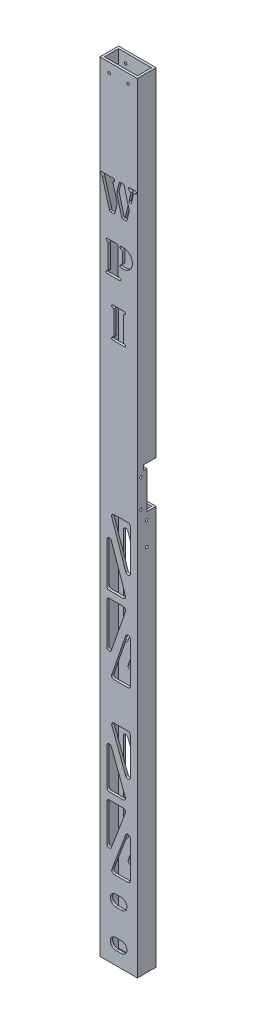
SolidWorks part; units mm, degrees
material "6061-T6 (SS)"
ref_plane "Front Plane" through (0, 0, 0) normal (0, 0, 1) x (1, 0, 0)
ref_plane "Top Plane" through (0, 0, 0) normal (0, 1, 0) x (1, 0, 0)
ref_plane "Right Plane" through (0, 0, 0) normal (1, 0, 0) x (0, 0, -1)
sketch "Sketch1" plane through (0, 0, 0) normal (0, 1, 0) x (1, 0, 0)
  line L0 (-22.225, 9.525) -> (-22.225, 12.7) construction
  line L1 (-25.4, -12.7) -> (25.4, -12.7)
  line L2 (-25.4, -12.7) -> (-25.4, 12.7)
  line L3 (-25.4, 12.7) -> (25.4, 12.7)
  line L4 (25.4, -12.7) -> (25.4, 12.7)
  line L5 (-25.4, -12.7) -> (25.4, 12.7) construction
  line L6 (-25.4, 12.7) -> (25.4, -12.7) construction
  line L7 (-22.225, -9.525) -> (22.225, -9.525)
  line L8 (-22.225, -9.525) -> (-22.225, 9.525)
  line L9 (-22.225, 9.525) -> (22.225, 9.525)
  line L10 (22.225, -9.525) -> (22.225, 9.525)
  line L11 (-22.225, -9.525) -> (22.225, 9.525) construction
  line L12 (-22.225, 9.525) -> (22.225, -9.525) construction
  line L13 (-22.225, 9.525) -> (-25.4, 9.525) construction
  point P0 (0, 0)
  point P6 (0, 0)
  dimension "D1" = 50.8
  dimension "D2" = 25.4
  dimension "D3" = 3.175
extrude "Boss-Extrude1" add sketch "Sketch1" along normal mid plane 591.185
hole_wizard "M8 Clearance Hole1" positions "Sketch3" profile "Sketch4" hole size "M8" standard "ANSI Metric" end condition through all
sketch "Sketch3" plane through (0, 0, 12.7) normal (0, 0, 1) x (1, 0, 0)
  line L1 (-25.4, -295.5925) -> (25.4, -295.5925) construction
  line L2 (0, -193.9925) -> (-50000, -193.9925) construction
  line L3 (-3.8049, -270.1925) -> (-3.8049, -295.5925) construction
  line L6 (-3.8049, -219.3925) -> (-3.8049, -193.9925) construction
  line L7 (0, 0) -> (0, 50000) construction
  point P0 (-3.8049, -270.1925)
  point P2 (-3.8049, -219.3925)
  point P29 (3.8049, -219.3925)
  point P31 (3.8049, -270.1925)
  dimension "D1" = 101.6
  dimension "D2" = 50.8
  dimension "D3" = 3.8049
sketch "Sketch4" plane through (-3.8049, -270.1925, 12.7) normal (1, 0, 0) x (0, -1, 0)
  line L0 (0, 0) -> (0, 25.4)
  line L1 (0, 25.4) -> (4.2, 25.4)
  line L2 (4.2, 25.4) -> (4.2, 0)
  line L5 (4.2, 0) -> (0, 0)
  line L11 (0, -6.35) -> (0, 107.95) construction
  dimension "Thru Hole Dia." = 8.4
  dimension "Thru Hole Depth" = 25.4
sketch "Sketch5" plane through (0, 295.5925, 0) normal (0, 1, 0) x (1, 0, 0)
  line L0 (-25.4, -4.572) -> (-22.225, -4.572)
  line L1 (-25.4, 12.7) -> (-25.4, -12.7) construction
  line L2 (-22.225, 9.525) -> (-22.225, -9.525) construction
  line L3 (-22.225, -4.572) -> (-22.225, -9.525)
  line L4 (-22.225, -9.525) -> (22.225, -9.525)
  line L5 (22.225, -9.525) -> (22.225, -4.572)
  line L6 (22.225, -9.525) -> (22.225, 9.525) construction
  line L7 (22.225, -4.572) -> (25.4, -4.572)
  line L8 (25.4, -12.7) -> (25.4, 12.7) construction
  line L9 (25.4, -4.572) -> (25.4, -12.7)
  line L10 (25.4, -12.7) -> (-25.4, -12.7)
  line L11 (-25.4, -12.7) -> (-25.4, -4.572)
  dimension "D1" = 8.128
extrude "Boss-Extrude2" add sketch "Sketch5" along normal blind 6.35
sketch "Sketch6" plane through (0, 301.9425, 0) normal (0, 1, 0) x (1, 0, 0)
  line L1 (-25.4, -12.7) -> (25.4, -12.7)
  line L2 (-25.4, -12.7) -> (-25.4, 12.7)
  line L3 (-25.4, 12.7) -> (25.4, 12.7)
  line L4 (25.4, -12.7) -> (25.4, 12.7)
  line L5 (-22.225, -9.525) -> (22.225, -9.525)
  line L6 (-22.225, -9.525) -> (-22.225, 9.525)
  line L7 (-22.225, 9.525) -> (22.225, 9.525)
  line L8 (22.225, -9.525) -> (22.225, 9.525)
extrude "Boss-Extrude3" add sketch "Sketch6" along normal blind 457.2
sketch "Sketch7" plane through (25.4, 0, 0) normal (1, 0, 0) x (0, 0, -1)
  line L1 (12.7, 295.5925) -> (0, 295.5925)
  line L2 (12.7, 295.5925) -> (12.7, 244.7925)
  line L3 (12.7, 244.7925) -> (0, 244.7925)
  line L4 (0, 295.5925) -> (0, 244.7925)
  dimension "D1" = 50.8
  dimension "D2" = 12.7
extrude "Cut-Extrude1" cut sketch "Sketch7" against normal up to surface (50.8 mm away) up to face at (-25.4, 265.6681, -4.191)
hole_wizard "#8-32 Tapped Hole1" positions "Sketch15" profile "Sketch14" tap size "#8-32" standard "ANSI Inch" end condition through all
sketch "Sketch15" plane through (-25.4, 0, 0) normal (-1, 0, 0) x (0, 0, 1)
  line L0 (0, 244.7925) -> (12.7, 244.7925) construction
  line L1 (12.7, 759.1425) -> (12.7, -295.5925) construction
  line L4 (0, 295.5925) -> (12.7, 295.5925) construction
  line L10 (0, 244.7925) -> (0, 295.5925) construction
  line L11 (0.6862, 219.3925) -> (-49999.3138, 219.3925) construction
  line L12 (-12.7, 244.7925) -> (0, 244.7925) construction
  line L13 (7.9375, 295.5925) -> (7.9375, 244.7925) construction
  line L15 (7.9375, 270.1925) -> (-49992.0625, 270.1925) construction
  point P0 (7.9375, 289.2425)
  point P2 (7.9375, 251.1425)
  point P4 (0, 235.2675)
  point P6 (0, 203.5175)
  point P55 (7.9375, 270.1925)
  dimension "D1" = 4.7625
  dimension "D2" = 31.75
  dimension "D3" = 25.4
  dimension "D4" = 38.1
sketch "Sketch14" plane through (-25.4, 289.2425, 7.9375) normal (0, 1, 0) x (0, 0, 1)
  line L0 (0, 0) -> (0, 50.8)
  line L1 (0, 50.8) -> (1.7272, 50.8)
  line L2 (1.7272, 50.8) -> (1.7272, 0)
  line L5 (1.7272, 0) -> (0, 0)
  line L11 (0, -6.35) -> (0, 107.95) construction
  dimension "Thru Tap Drill Dia." = 3.4544
  dimension "Thru Tap Drill Depth" = 50.8
cosmetic thread "Hole Thread1" parameters "D2"=4.1656
cosmetic thread "Hole Thread2" parameters "D2"=4.1656
cosmetic thread "Hole Thread3" parameters "D2"=4.1656
cosmetic thread "Hole Thread4" parameters "D2"=4.1656
sketch "Sketch16" plane through (0, 0, 12.7) normal (0, 0, 1) x (1, 0, 0)
  line L0 (-3.8049, -219.3925) -> (3.8049, -219.3925) construction
  line L1 (-3.8049, -211.8925) -> (3.8049, -211.8925)
  line L2 (-3.8049, -226.8925) -> (3.8049, -226.8925)
  line L3 (-3.8049, -270.1925) -> (3.8049, -270.1925) construction
  line L4 (-3.8049, -262.6925) -> (3.8049, -262.6925)
  line L5 (-3.8049, -277.6925) -> (3.8049, -277.6925)
  arc A0 (-3.8049, -211.8925) -> (-3.8049, -226.8925) centre (-3.8049, -219.3925) ccw
  arc A1 (3.8049, -226.8925) -> (3.8049, -211.8925) centre (3.8049, -219.3925) ccw
  arc A2 (-3.8049, -262.6925) -> (-3.8049, -277.6925) centre (-3.8049, -270.1925) ccw
  arc A3 (3.8049, -277.6925) -> (3.8049, -262.6925) centre (3.8049, -270.1925) ccw
  point P4 (0, -219.3925)
  point P13 (0, -270.1925)
  dimension "D1" = 7.5
extrude "Cut-Extrude4" cut sketch "Sketch16" against normal up to next
sketch "Sketch9" plane through (0, 0, -12.7) normal (0, 0, -1) x (0, -1, 0)
  line L0 (-167.6278, 15.875) -> (-50167.6278, 15.875) construction
  line L1 (-187.0451, -15.875) -> (-50187.0451, -15.875) construction
  line L2 (189.7925, -2.3398) -> (189.7925, 49997.6602) construction
  line L3 (-232.0925, -4.2977) -> (-232.0925, 49995.7023) construction
  line L4 (-244.7925, 25.4) -> (295.5925, 25.4) construction
  line L5 (-244.7925, -25.4) -> (295.5925, -25.4) construction
  line L6 (-244.7925, 25.4) -> (-244.7925, -25.4) construction
  line L7 (-232.0925, 15.875) -> (-232.0925, -15.875) construction
  line L8 (-140.0175, -15.875) -> (-232.0925, -15.875) construction
  line L9 (-140.0175, -15.875) -> (-140.0175, 15.875) construction
  line L10 (-140.0175, 15.875) -> (-232.0925, 15.875) construction
  line L11 (-232.0925, -15.875) -> (-232.0925, 15.875) construction
  line L12 (-140.0175, -15.875) -> (-232.0925, 15.875) construction
  line L13 (-140.0175, 15.875) -> (-232.0925, -15.875) construction
  line L14 (-232.0925, 0) -> (-50232.0925, 0) construction
  line L15 (105.85, 15.875) -> (96.325, 15.875) construction
  line L16 (-38.4175, -15.875) -> (-130.4925, -15.875) construction
  line L17 (-38.4175, -15.875) -> (-38.4175, 15.875) construction
  line L18 (-38.4175, 15.875) -> (-130.4925, 15.875) construction
  line L19 (-130.4925, -15.875) -> (-130.4925, 15.875) construction
  line L20 (-38.4175, -15.875) -> (-130.4925, 15.875) construction
  line L21 (-38.4175, 15.875) -> (-130.4925, -15.875) construction
  line L22 (96.325, -15.875) -> (12.3825, -15.875) construction
  line L23 (96.325, -15.875) -> (96.325, 15.875) construction
  line L24 (96.325, 15.875) -> (12.3825, 15.875) construction
  line L25 (12.3825, -15.875) -> (12.3825, 15.875) construction
  line L26 (96.325, -15.875) -> (12.3825, 15.875) construction
  line L27 (96.325, 15.875) -> (12.3825, -15.875) construction
  line L28 (189.7925, -15.875) -> (105.85, -15.875) construction
  line L29 (189.7925, -15.875) -> (189.7925, 15.875) construction
  line L30 (189.7925, 15.875) -> (105.85, 15.875) construction
  line L31 (105.85, -15.875) -> (105.85, 15.875) construction
  line L32 (189.7925, -15.875) -> (105.85, 15.875) construction
  line L33 (189.7925, 15.875) -> (105.85, -15.875) construction
  line L34 (-115.8832, -15.875) -> (-118.9882, -6.8703) construction
  line L35 (-140.0175, 15.875) -> (-130.4925, 15.875) construction
  line L36 (189.7925, -15.875) -> (189.7925, 10.7832)
  line L37 (189.7925, 10.7832) -> (119.312, -15.875)
  line L38 (119.312, -15.875) -> (189.7925, -15.875)
  line L39 (101.0875, 15.875) -> (101.0875, 50015.875) construction
  line L40 (105.85, 15.875) -> (176.3305, 15.875)
  line L41 (176.3305, 15.875) -> (105.85, -10.7832)
  line L42 (105.85, -10.7832) -> (105.85, 15.875)
  line L43 (119.312, -15.875) -> (115.9422, -6.966) construction
  line L44 (96.325, -10.7832) -> (96.325, 15.875)
  line L45 (96.325, 15.875) -> (25.8445, 15.875)
  line L46 (25.8445, 15.875) -> (96.325, -10.7832)
  line L47 (12.3825, 10.7832) -> (82.863, -15.875)
  line L48 (12.3825, -15.875) -> (12.3825, 10.7832)
  line L49 (82.863, -15.875) -> (12.3825, -15.875)
  line L50 (-154.6268, -15.875) -> (-151.5218, -6.8703) construction
  line L51 (-232.0925, -15.875) -> (-232.0925, 10.8373)
  line L52 (-154.6268, -15.875) -> (-232.0925, -15.875)
  line L53 (-232.0925, 10.8373) -> (-154.6268, -15.875)
  line L54 (-217.4832, 15.875) -> (-140.0175, -10.8373)
  line L55 (-140.0175, -10.8373) -> (-140.0175, 15.875)
  line L56 (-140.0175, 15.875) -> (-217.4832, 15.875)
  line L57 (-130.4925, 15.875) -> (-53.0268, 15.875)
  line L58 (-130.4925, -10.8373) -> (-130.4925, 15.875)
  line L59 (-53.0268, 15.875) -> (-130.4925, -10.8373)
  line L60 (-115.8832, -15.875) -> (-38.4175, -15.875)
  line L61 (-38.4175, 10.8373) -> (-115.8832, -15.875)
  line L62 (-38.4175, -15.875) -> (-38.4175, 10.8373)
  line L63 (-13.0175, 80.4907) -> (-13.0175, 50080.4907) construction
  line L64 (295.5925, -25.4) -> (295.5925, 25.4) construction
  line L65 (-38.4175, 0) -> (-38.4175, 50000) construction
  circle A0 centre (219.3925, 3.8049) radius 4.2 construction
  circle A3 centre (219.3925, 3.8049) radius 29.6 construction
  point P17 (-186.055, 0)
  point P27 (-232.0925, 0)
  point P28 (-84.455, 0)
  point P33 (54.3537, 0)
  point P38 (147.8213, 0)
  point P45 (101.0875, 15.875)
  point P52 (117.6271, -11.4205)
  dimension "D4" = 25.4
  dimension "D1" = 9.525
  dimension "D3" = 12.7
  dimension "D2" = 9.525
  dimension "D5" = 9.525
  dimension "D6" = 9.525
  dimension "D7" = 308.61
  dimension "D8" = 9.525
  dimension "D9" = 25.4
  dimension "D10" = 25.4
  dimension "D11" = 0
  dimension "D12" = 9.525
extrude "Cut-Extrude2" cut sketch "Sketch9" against normal through all contours L53 L51 L52 | L55 L56 L54 | L59 L57 L58 | L60 L62 L61 | L49 L47 L48 | L45 L46 L44 | L42 L41 L40 | L37 L38 L36 region at (6.9889, -166.299, -12.7) region at (-6.9889, -129.3435, -12.7) region at (-6.9889, -72.8315, -12.7) region at (6.9889, -35.876, -12.7) region at (6.9709, 206.2706, -12.7) region at (-6.9709, 165.8394, -12.7) region at (-6.9709, 104.6706, -12.7) region at (6.9709, 64.2394, -12.7)
fillet "Fillet1" radius 3.175 48 edges at (15.875, -82.863, 11.1125) (15.875, 38.4175, -11.1125) (15.875, 38.4175, 11.1125) (-10.8373, 38.4175, -11.1125) (-10.8373, 38.4175, 11.1125) (15.875, 115.8832, 11.1125) (15.875, 115.8832, -11.1125) (-15.875, 130.4925, -11.1125) (-15.875, 130.4925, 11.1125) (-15.875, 53.0268, 11.1125) (-15.875, 53.0268, -11.1125) (-15.875, 140.0175, -11.1125) (-15.875, 140.0175, 11.1125) (15.875, 154.6268, 11.1125) (15.875, 154.6268, -11.1125) (-15.875, 217.4832, -11.1125) (-15.875, 217.4832, 11.1125) (-10.8373, 232.0925, 11.1125) (-10.8373, 232.0925, -11.1125) (10.8373, 140.0175, 11.1125) (10.8373, 140.0175, -11.1125) (10.8373, 130.4925, 11.1125) (10.8373, 130.4925, -11.1125) (15.875, 232.0925, 11.1125) (15.875, 232.0925, -11.1125) (10.7832, -96.325, 11.1125) (10.7832, -96.325, -11.1125) (10.7832, -105.85, -11.1125) (10.7832, -105.85, 11.1125) (-15.875, -25.8445, 11.1125) (-15.875, -25.8445, -11.1125) (15.875, -12.3825, -11.1125) (15.875, -12.3825, 11.1125) (15.875, -119.312, 11.1125) (15.875, -119.312, -11.1125) (-15.875, -176.3305, 11.1125) (-15.875, -176.3305, -11.1125) (-15.875, -105.85, -11.1125) (-15.875, -105.85, 11.1125) (-10.7832, -12.3825, -11.1125) (-10.7832, -12.3825, 11.1125) (-15.875, -96.325, -11.1125) (-15.875, -96.325, 11.1125) (-10.7832, -189.7925, -11.1125) (-10.7832, -189.7925, 11.1125) (15.875, -189.7925, -11.1125) (15.875, -189.7925, 11.1125) (15.875, -82.863, -11.1125)
hole_wizard "#8-32 Tapped Hole2" positions "Sketch18" profile "Sketch17" tap size "#8-32" standard "ANSI Inch" end condition up to next
sketch "Sketch18" plane through (0, 0, -12.7) normal (0, 0, -1) x (-1, 0, 0)
  line L0 (0, 0) -> (0, 50000) construction
  line L1 (0, 13.0175) -> (-50000, 13.0175) construction
  line L2 (-16.0353, 0.3175) -> (-50016.0353, 0.3175) construction
  line L3 (-12.7, 38.4175) -> (6.384, 38.4175) construction
  point P0 (-15.875, 0.3175)
  point P2 (15.875, 0.3175)
  point P15 (-3.158, 38.4175)
  dimension "D1" = 25.4
  dimension "D2" = 12.7
  dimension "D3" = 31.75
sketch "Sketch17" plane through (15.875, 0.3175, -12.7) normal (1, 0, 0) x (0, 1, 0)
  line L0 (0, 0) -> (0, 3.175)
  line L1 (0, 3.175) -> (1.7272, 3.175)
  line L2 (1.7272, 3.175) -> (1.7272, 0)
  line L5 (1.7272, 0) -> (0, 0)
  line L11 (0, -6.35) -> (0, 107.95) construction
  dimension "Thru Tap Drill Dia." = 3.4544
  dimension "Thru Tap Drill Depth" = 3.175
cosmetic thread "Hole Thread5" parameters "D2"=4.1656
cosmetic thread "Hole Thread6" parameters "D2"=4.1656
sketch "Sketch13" plane through (0, 0, -12.7) normal (0, 0, -1) x (-1, 0, 0)
  line L0 (-25.4, 622.6175) -> (25.4, 622.6175) construction
  line L1 (25.4, 759.1425) -> (25.4, 301.9425) construction
  line L2 (-25.4, 759.1425) -> (-25.4, 301.9425) construction
  line L3 (-25.4, 301.9425) -> (-25.4, 759.1425) construction
  line L4 (-25.4, 530.5425) -> (-50025.4, 530.5425) construction
  line L5 (-92.9548, 667.0675) -> (-50092.9548, 667.0675) construction
  text T0 "R\r\nA\r\nI\r\nL" font "Stencil" height 44.45
  point P15 (-25.4, 530.5425)
  dimension "D1" = 44.45
  dimension "D2" = 136.525
extrude "Cut-Extrude3" cut sketch "Sketch13" against normal up to surface (3.175 mm away) up to face at (0, 530.5425, -9.525)
fillet "Fillet2" radius 1.5875 16 edges at (-2.4694, 382.5508, -11.1125) (-17.9035, 382.5508, -11.1125) (-5.5562, 382.5508, -11.1125) (-5.5562, 386.1971, -11.1125) (3.0868, 667.0675, -11.1125) (0.5884, 667.0675, -11.1125) (0.5884, 663.4501, -11.1125) (0.6174, 642.1223, -11.1125) (0.6174, 645.5853, -11.1125) (-8.1607, 587.0453, -11.1125) (4.9582, 587.0453, -11.1125) (5.7685, 583.8041, -11.1125) (7.9485, 553.7078, -11.1125) (7.0707, 557.4119, -11.1125) (7.2058, 578.653, -11.1125) (5.5466, 571.8813, -11.1125)
sketch "Sketch20" plane through (0, 0, 12.7) normal (0, 0, 1) x (1, 0, 0)
  line L0 (-25.4, 584.5175) -> (25.4, 584.5175) construction
  line L1 (-25.4, 759.1425) -> (25.4, 759.1425) construction
  line L2 (25.4, 301.9425) -> (-25.4, 301.9425) construction
  line L3 (25.4, 301.9425) -> (-25.4, 301.9425) construction
  line L4 (0, 301.9425) -> (0, 759.1425) construction
  line L5 (178.8188, 530.5425) -> (-49821.1812, 530.5425) construction
  line L6 (-25.4, 759.1425) -> (-25.4, -295.5925) construction
  line L7 (25.4, 759.1425) -> (25.4, -295.5925) construction
  line L8 (-74.2291, 625.7925) -> (-50074.2291, 625.7925) construction
  text T0 "W\r\nP\r\nI" font "Stencil" height 41.275
  point P4 (0, 759.1425)
  point P11 (0, 530.5425)
  dimension "D1" = 95.25
  dimension "D2" = 41.275
extrude "Cut-Extrude5" cut sketch "Sketch20" against normal up to surface (3.175 mm away) up to face at (0, 524.5327, 9.525)
fillet "Fillet3" radius 1.5875 19 edges at (7.2492, 625.7925, 11.1125) (1.0239, 625.7925, 11.1125) (-2.5769, 610.9593, 11.1125) (14.5045, 598.2042, 11.1125) (-5.506, 584.5175, 11.1125) (-12.0358, 584.5175, 11.1125) (-1.8514, 599.082, 11.1125) (4.4724, 584.5175, 11.1125) (11.056, 584.5175, 11.1125) (2.0064, 525.8687, 11.1125) (2.0064, 529.0843, 11.1125) (-14.8601, 510.1397, 11.1125) (-16.9113, 511.7072, 11.1125) (-15.7916, 513.3285, 11.1125) (-16.9113, 549.8203, 11.1125) (-14.8601, 551.4147, 11.1125) (2.0333, 548.1453, 11.1125) (2.0333, 551.4147, 11.1125) (-0.8599, 551.4147, 11.1125)
sketch "Sketch22" plane through (0, 0, 12.7) normal (0, 0, 1) x (1, 0, 0)
  line L0 (15.7922, 602.474) -> (18.8985, 615.785)
  line L1 (14.0836, 609.1231) -> (16.1885, 618.143) construction
  line L2 (19.3504, 617.5608) -> (15.6511, 603.0232) construction
  line L3 (15.6511, 603.0232) -> (14.0836, 609.1231) construction
  line L4 (15.7922, 602.474) -> (15.6511, 603.0232)
  line L5 (15.6511, 603.0232) -> (18.8985, 615.785)
  dimension "D1" = 3.175
extrude "Cut-Extrude6" cut sketch "Sketch22" against normal up to next
sketch "Sketch23" plane through (0, 0, 12.7) normal (0, 0, 1) x (1, 0, 0)
  line L0 (14.0836, 609.1231) -> (16.1885, 618.143) construction
  line L1 (15.7922, 602.474) -> (18.8985, 615.785) construction
  line L2 (15.7922, 602.474) -> (14.0836, 609.1231) construction
  line L3 (14.172, 609.502) -> (14.0836, 609.1231)
  line L4 (14.0836, 609.1231) -> (15.7922, 602.474)
  line L5 (15.7922, 602.474) -> (17.2639, 608.7805)
  arc A0 (14.172, 609.502) -> (17.2639, 608.7805) centre (15.718, 609.1413) ccw
extrude "Boss-Extrude4" add sketch "Sketch23" against normal up to surface (3.175 mm away) contours A0 L4 L5 | A0 L3 L4 region at (14.121, 609.1235, 12.7) region at (15.7526, 606.0302, 12.7) up to face at (1.3754, 602.9273, 9.525)
hole_wizard "#8-32 Tapped Hole3" positions "Sketch25" profile "Sketch24" tap size "#8-32" standard "ANSI Inch" end condition up to next
sketch "Sketch25" plane through (0, 0, -12.7) normal (0, 0, -1) x (-1, 0, 0)
  line L0 (0, 301.9425) -> (0, 50301.9425) construction
  line L1 (-25.4, 301.9425) -> (25.4, 301.9425) construction
  point P0 (-19.05, 317.8175)
  point P2 (19.05, 317.8175)
  point P9 (0, 301.9425)
  dimension "D1" = 15.875
  dimension "D2" = 38.1
sketch "Sketch24" plane through (19.05, 317.8175, -12.7) normal (1, 0, 0) x (0, 1, 0)
  line L0 (0, 0) -> (0, 3.175)
  line L1 (0, 3.175) -> (1.7272, 3.175)
  line L2 (1.7272, 3.175) -> (1.7272, 0)
  line L5 (1.7272, 0) -> (0, 0)
  line L11 (0, -6.35) -> (0, 107.95) construction
  dimension "Thru Tap Drill Dia." = 3.4544
  dimension "Thru Tap Drill Depth" = 3.175
cosmetic thread "Hole Thread7" parameters "D2"=4.1656
cosmetic thread "Hole Thread8" parameters "D2"=4.1656
hole_wizard "#8-32 Tapped Hole4" positions "Sketch27" profile "Sketch26" tap size "#8-32" standard "ANSI Inch" end condition through all
sketch "Sketch27" plane through (0, 0, 12.7) normal (0, 0, 1) x (1, 0, 0)
  line L0 (0, 759.1425) -> (0, 50759.1425) construction
  line L1 (-25.4, 759.1425) -> (25.4, 759.1425) construction
  point P0 (-12.7, 746.4425)
  point P2 (12.7, 746.4425)
  point P9 (0, 759.1425)
  dimension "D1" = 25.4
  dimension "D2" = 12.7
sketch "Sketch26" plane through (-12.7, 746.4425, 12.7) normal (1, 0, 0) x (0, -1, 0)
  line L0 (0, 0) -> (0, 25.4)
  line L1 (0, 25.4) -> (1.7272, 25.4)
  line L2 (1.7272, 25.4) -> (1.7272, 0)
  line L5 (1.7272, 0) -> (0, 0)
  line L11 (0, -6.35) -> (0, 107.95) construction
  dimension "Thru Tap Drill Dia." = 3.4544
  dimension "Thru Tap Drill Depth" = 25.4
cosmetic thread "Hole Thread9" parameters "D2"=4.1656
cosmetic thread "Hole Thread10" parameters "D2"=4.1656
equation "\"D1@Boss-Extrude1\"=21+4-1.85+.125"
equation "\"D1@Sketch15\"=.25-1/16"
